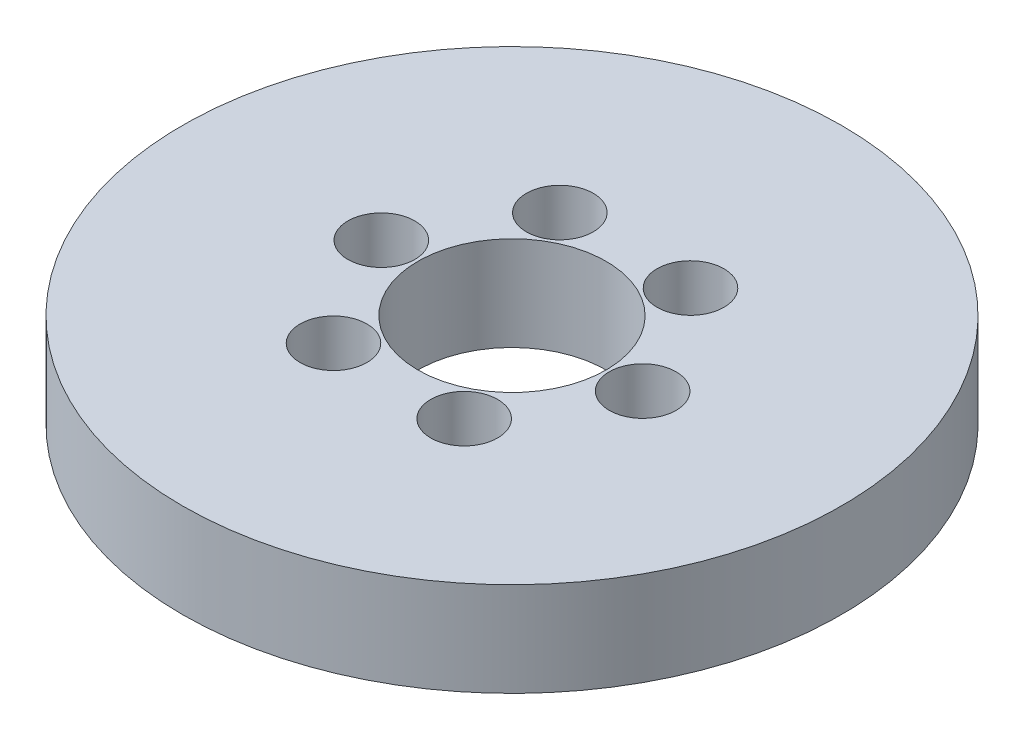
SolidWorks part; units mm, degrees
ref_plane "Front Plane" through (0, 0, 0) normal (0, 0, 1) x (1, 0, 0)
ref_plane "Top Plane" through (0, 0, 0) normal (0, 1, 0) x (1, 0, 0)
ref_plane "Right Plane" through (0, 0, 0) normal (1, 0, 0) x (0, 0, -1)
sketch "Sketch1" plane through (0, 0, 0) normal (0, 1, 0) x (1, 0, 0)
  circle A0 centre (0, 0) radius 70
  dimension "FLANGE_OD" = 140
extrude "Boss-Extrude1" add sketch "Sketch1" along normal blind 20
sketch "Sketch2" plane through (0, 0, 0) normal (0, 1, 0) x (1, 0, 0)
  circle A0 centre (0, 0) radius 20
  dimension "BORE_D" = 40
extrude "Cut-Extrude1" cut sketch "Sketch2" along normal through all
sketch "Sketch3" plane through (0, 20, 0) normal (0, 1, 0) x (1, 0, 0)
  circle A0 centre (0, 0) radius 27.7538 construction
  circle A1 centre (-27.7538, 0) radius 7.1058
  dimension "BOLT_D" = 14.2116
  dimension "BOLT_PCD" = 55.5076
extrude "Cut-Extrude2" cut sketch "Sketch3" against normal blind 12.3723
pattern_circular "CirPattern1" count 6 over 360 about axis through (0, 0, 0) along (0, 1, 0) of "Cut-Extrude2"
